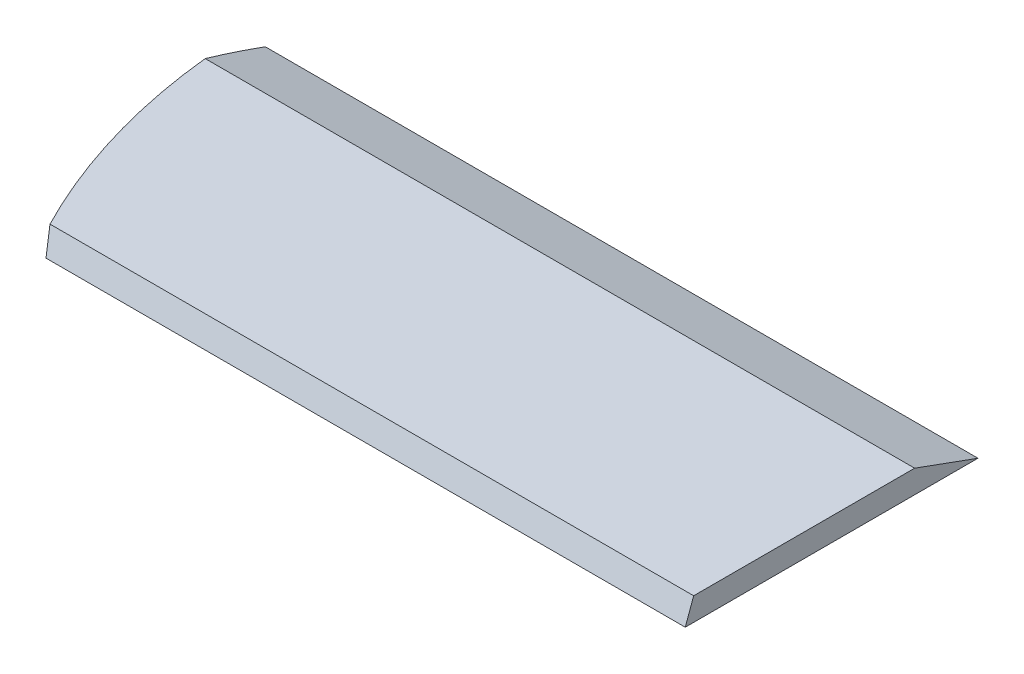
SolidWorks part; units mm, degrees
ref_plane "Front Plane" through (0, 0, 0) normal (0, 0, 1) x (1, 0, 0)
ref_plane "Top Plane" through (0, 0, 0) normal (0, 1, 0) x (1, 0, 0)
ref_plane "Right Plane" through (0, 0, 0) normal (1, 0, 0) x (0, 0, -1)
sketch "Sketch1" plane through (0, 0, 0) normal (0, 1, 0) x (1, 0, 0)
  line L1 (-277.1757, 0) -> (0, 0)
  line L3 (-309, 126.92) -> (0, 126.92)
  line L4 (0, 0) -> (0, 126.92)
  arc A0 (-309, 126.92) -> (-277.1757, 0) centre (-40, 126.92) ccw
  point P0 (0, 0)
  point P7 (31.8242, 0)
  dimension "D3" = 269
  dimension "D1" = 309
  dimension "D2" = 126.92
  dimension "D4" = 40
extrude "Boss-Extrude1" add sketch "Sketch1" along normal blind 10
chamfer "Chamfer1" distance 10 angle 70 1 edges at (-154.5, 10, -126.92) first distance on face at (-154.5, 5, -126.92)
chamfer "Chamfer3" distance 10 angle 20 1 edges at (-138.5879, 10, 0) first distance on face at (-138.5879, 5, 0)
